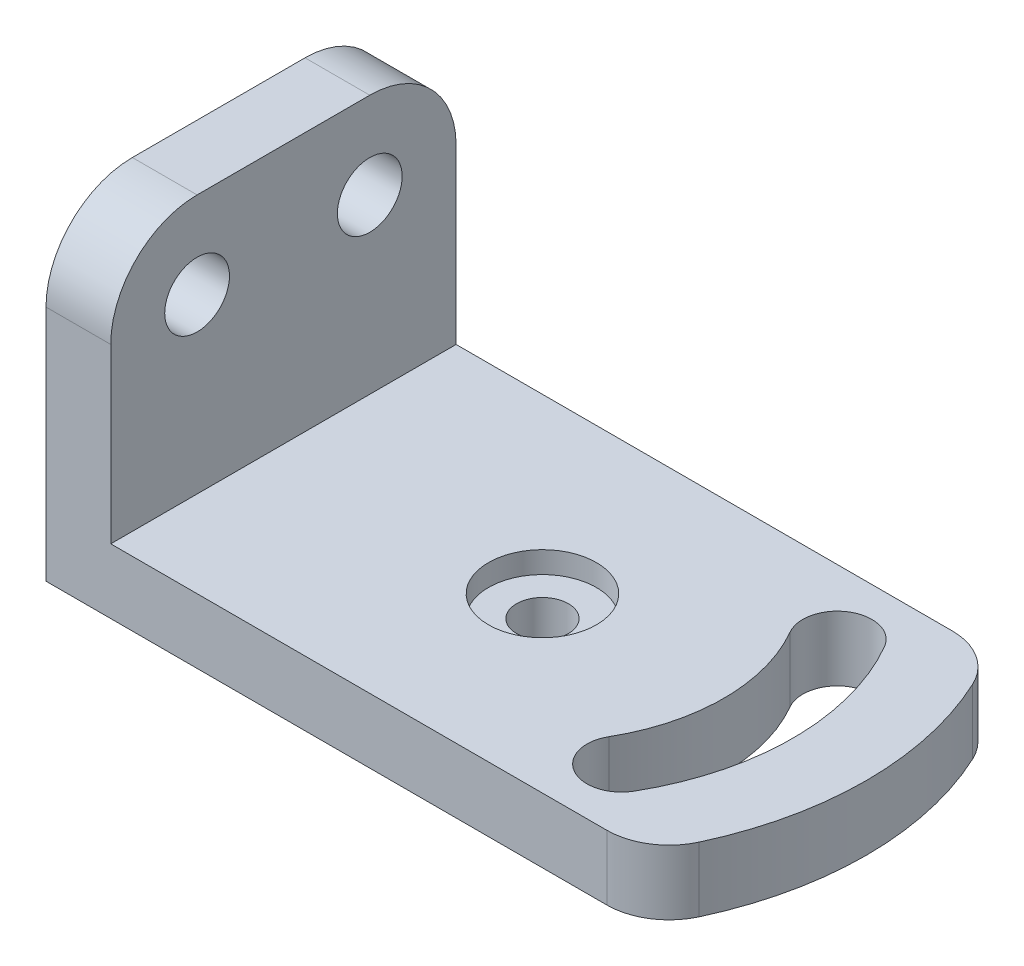
SolidWorks part; units mm, degrees
ref_plane "Front Plane" through (0, 0, 0) normal (0, 0, 1) x (1, 0, 0)
ref_plane "Top Plane" through (0, 0, 0) normal (0, 1, 0) x (1, 0, 0)
ref_plane "Right Plane" through (0, 0, 0) normal (1, 0, 0) x (0, 0, -1)
sketch "Sketch1" plane through (0, 0, 0) normal (0, 1, 0) x (1, 0, 0)
  line L0 (0, 40) -> (0, -40)
  line L1 (0, -40) -> (15, -40)
  line L2 (15, -40) -> (15, 40)
  line L3 (15, 40) -> (0, 40)
  line L4 (15, 40) -> (129.9283, 40)
  line L5 (15, -40) -> (129.9283, -40)
  line L6 (-8.7922, 0) -> (144.3254, 0) construction
  line L7 (118.3013, 25) -> (75, 0) construction
  arc A0 (118.3013, 25) -> (118.3013, -25) centre (75, 0) cw construction
  arc A1 (125.2295, -29) -> (125.2295, 29) centre (75, 0) ccw
  arc A2 (111.3731, -21) -> (111.3731, 21) centre (75, 0) ccw
  arc A3 (111.3731, -21) -> (125.2295, -29) centre (118.3013, -25) ccw
  arc A4 (125.2295, 29) -> (111.3731, 21) centre (118.3013, 25) ccw
  circle A5 centre (75, 0) radius 12.5
  circle A6 centre (75, 0) radius 6
  arc A7 (129.9283, 40) -> (142.9787, 31.6844) centre (129.9283, 25.6018) cw
  arc A8 (142.9787, 31.6844) -> (142.9787, -31.6844) centre (75, 0) cw
  arc A9 (142.9787, -31.6844) -> (129.9283, -40) centre (129.9283, -25.6018) cw
  point P10 (125, 0)
  point P20 (0, 0)
  point P25 (116.8252, 0)
  point P26 (150, 0)
  point P27 (75, 0)
  dimension "D1" = 80
  dimension "D2" = 8
  dimension "D3" = 50
  dimension "D4" = 75
  dimension "D5" = 25
  dimension "D6" = 12
  dimension "D10" = 14.3982
  dimension "D7" = 150
  dimension "D8" = 15
  dimension "D9" = 75
  dimension "D11" = 30
extrude "Boss-Extrude1" add sketch "Sketch1" along normal blind 75 contours L2 L3 L0 L1 region at (7.5, 0, 0)
extrude "Boss-Extrude2" add sketch "Sketch1<3>" along normal blind 15 contours A9 A8 A7 L4 L2 L5 A5 A4 A1 A3 A2 region at (72.4642, 0, -38.4308)
sketch "Sketch1<3>" plane through (0, 0, 0) normal (0, 1, 0) x (1, 0, 0) same geometry as "Sketch1"
extrude "Boss-Extrude3" add sketch "Sketch1<4>" along normal blind 10 contours A5 A6 region at (62.8536, 0, 0)
sketch "Sketch1<4>" plane through (0, 0, 0) normal (0, 1, 0) x (1, 0, 0) same geometry as "Sketch1"
sketch "Sketch2" plane through (15, 0, 0) normal (1, 0, 0) x (0, 0, -1)
  line L0 (-40, 75) -> (40, 75) construction
  line L1 (0, -1.7221) -> (0, 6.4023) construction
  line L2 (-40, 75) -> (-40, 15) construction
  circle A0 centre (-20, 55) radius 7.5
  circle A1 centre (-20, 55) radius 20
  circle A2 centre (20, 55) radius 20
  circle A3 centre (20, 55) radius 7.5
  line M2 (-40, 75) -> (-40, 15)
  line M4 (40, 15) -> (40, 75)
  line M5 (40, 75) -> (-40, 75)
  dimension "D1" = 40
  dimension "D2" = 15
extrude "Cut-Extrude1" cut sketch "Sketch2" against normal through all both and the other way through all contours A2 M5 M4 | A3 | A0 | A1 M5 M2 region at (15, 55, 20) region at (15, 70.5326, 35.5326) region at (15, 70.5326, -35.5326) region at (15, 55, -20)
